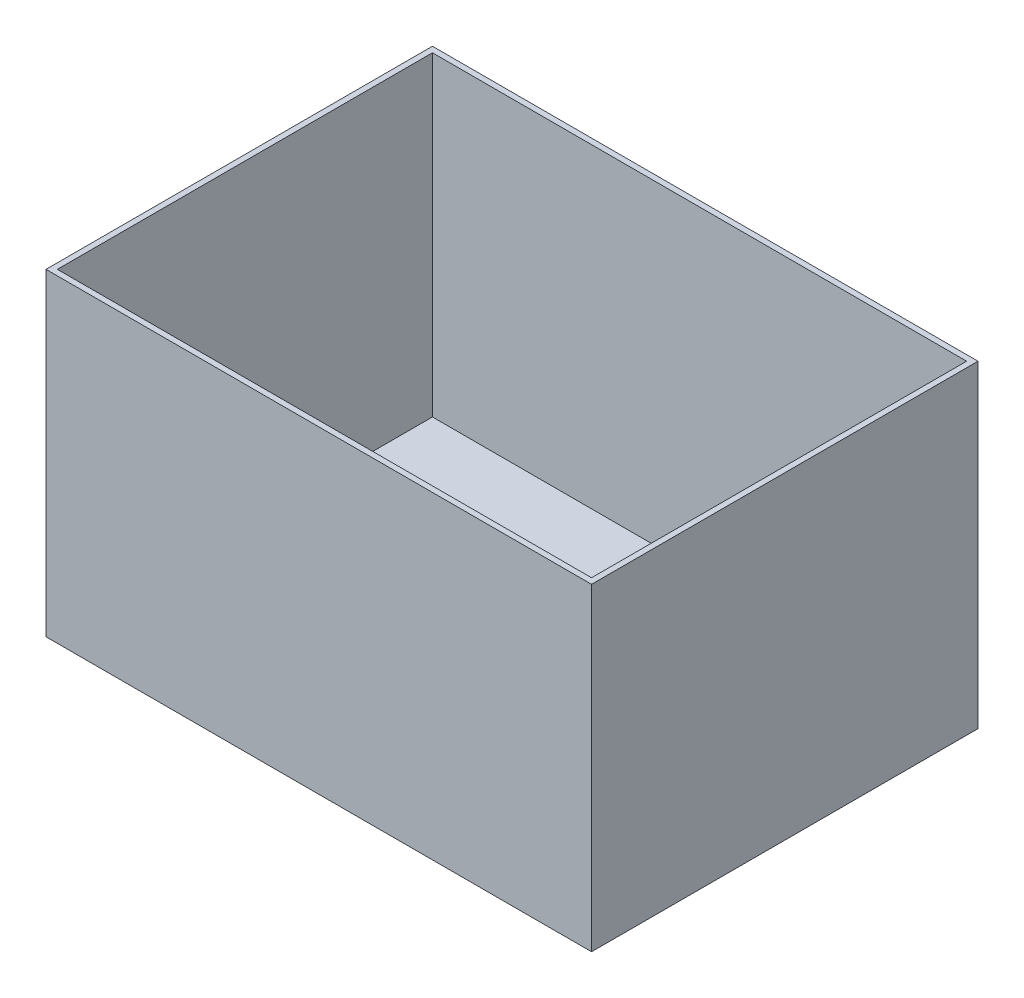
SolidWorks part; units mm, degrees
ref_plane "Front Plane" through (0, 0, 0) normal (0, 0, 1) x (1, 0, 0)
ref_plane "Top Plane" through (0, 0, 0) normal (0, 1, 0) x (1, 0, 0)
ref_plane "Right Plane" through (0, 0, 0) normal (1, 0, 0) x (0, 0, -1)
sketch "Sketch1" plane through (0, 0, 0) normal (0, 1, 0) x (1, 0, 0)
  line L0 (-149.225, 107.95) -> (-149.225, 104.775) construction
  line L1 (-152.4, 107.95) -> (152.4, 107.95)
  line L2 (-152.4, 107.95) -> (-152.4, -107.95)
  line L3 (-152.4, -107.95) -> (152.4, -107.95)
  line L4 (152.4, 107.95) -> (152.4, -107.95)
  line L5 (-152.4, 107.95) -> (152.4, -107.95) construction
  line L6 (-152.4, -107.95) -> (152.4, 107.95) construction
  line L7 (-149.225, -104.775) -> (149.225, -104.775)
  line L8 (-149.225, -104.775) -> (-149.225, 104.775)
  line L9 (-149.225, 104.775) -> (149.225, 104.775)
  line L10 (149.225, -104.775) -> (149.225, 104.775)
  line L11 (-149.225, -104.775) -> (149.225, 104.775) construction
  line L12 (-149.225, 104.775) -> (149.225, -104.775) construction
  line L13 (-149.225, 104.775) -> (-152.4, 104.775) construction
  point P0 (0, 0)
  point P6 (0, 0)
  dimension "D1" = 304.8
  dimension "D2" = 215.9
  dimension "D3" = 3.175
extrude "Boss-Extrude1" add sketch "Sketch1" along normal mid plane 3.175 contours L7 L10 L9 L8 region at (0, 0, 0)
extrude "Boss-Extrude2" add sketch "Sketch1<3>" along normal blind 177.8
sketch "Sketch1<3>" plane through (0, 0, 0) normal (0, 1, 0) x (1, 0, 0) same geometry as "Sketch1"
